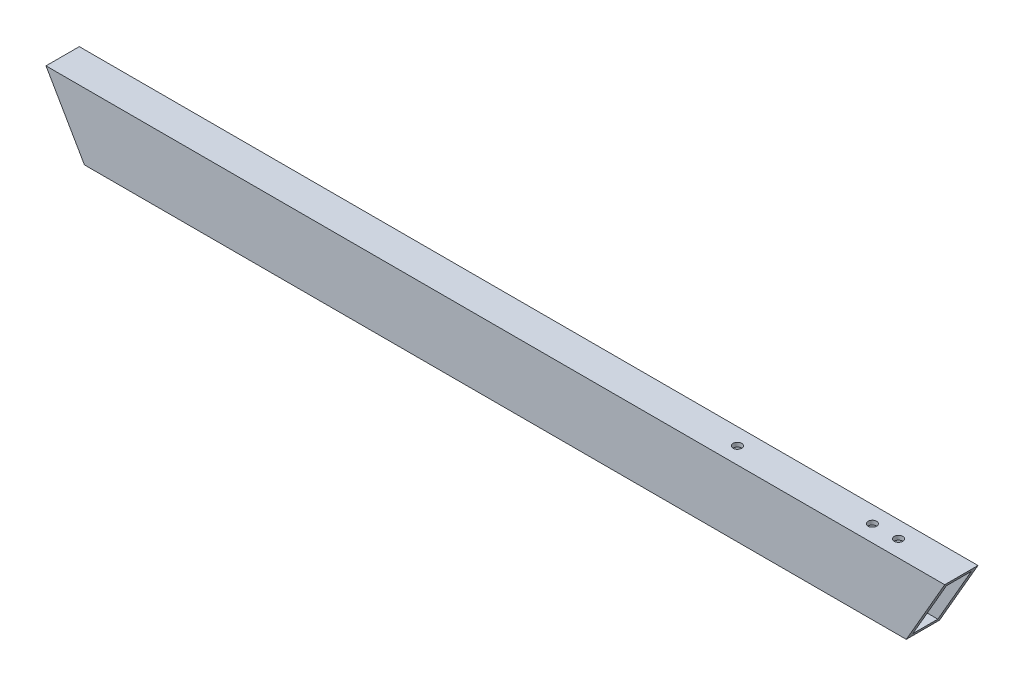
SolidWorks part; units mm, degrees
ref_plane "Front Plane" through (0, 0, 0) normal (0, 0, 1) x (1, 0, 0)
ref_plane "Top Plane" through (0, 0, 0) normal (0, 1, 0) x (1, 0, 0)
ref_plane "Right Plane" through (0, 0, 0) normal (1, 0, 0) x (0, 0, -1)
sketch "Sketch1" plane through (0, 0, 0) normal (1, 0, 0) x (0, 0, -1)
  line L1 (-9.525, -22.225) -> (9.525, -22.225)
  line L2 (-9.525, -22.225) -> (-9.525, 22.225)
  line L3 (-9.525, 22.225) -> (9.525, 22.225)
  line L4 (9.525, -22.225) -> (9.525, 22.225)
  line L5 (-9.525, -22.225) -> (9.525, 22.225) construction
  line L6 (-9.525, 22.225) -> (9.525, -22.225) construction
  line L7 (-12.7, -25.4) -> (12.7, -25.4)
  line L8 (-12.7, -25.4) -> (-12.7, 25.4)
  line L9 (-12.7, 25.4) -> (12.7, 25.4)
  line L10 (12.7, -25.4) -> (12.7, 25.4)
  line L11 (-12.7, -25.4) -> (12.7, 25.4) construction
  line L12 (-12.7, 25.4) -> (12.7, -25.4) construction
  point P0 (0, 0)
  point P6 (0, 0)
  dimension "D1" = 25.4
  dimension "D2" = 50.8
  dimension "D3" = 3.175
  dimension "D4" = 3.175
extrude "Boss-Extrude1" add sketch "Sketch1" along normal mid plane 685.8
sketch "Sketch2" plane through (0, 0, -12.7) normal (0, 0, -1) x (-1, 0, 0)
  line L0 (342.9, 25.4) -> (313.5706, -25.4)
  line L1 (-342.9, -25.4) -> (342.9, -25.4) construction
  line L3 (0, 13.97) -> (0, -13.97) construction
  line L4 (-342.9, 25.4) -> (-313.5706, -25.4)
  line M2 (342.9, -25.4) -> (342.9, 25.4)
  line M4 (-342.9, 25.4) -> (-342.9, -25.4)
  line M5 (-342.9, -25.4) -> (342.9, -25.4)
  dimension "D1" = 60
extrude "Cut-Extrude1" cut sketch "Sketch2" against normal through all and the other way through all contours L0 M2 M5 | L4 M4 M5 region at (-333.1235, -8.4667, -12.7) region at (333.1235, -8.4667, -12.7)
sketch "Sketch3" plane through (0, 0, -12.7) normal (0, 0, -1) x (-1, 0, 0)
  line L0 (-313.5706, -25.4) -> (313.5706, -25.4) construction
  circle A0 centre (-234.95, 0) radius 11.1125
  circle A1 centre (-190.5, 0) radius 11.1125
  dimension "D1" = 22.225
  dimension "D4" = 107.95
  dimension "D5" = 44.45
  dimension "D2" = 25.4
  dimension "D3" = 2
extrude "Cut-Extrude2" cut sketch "Sketch3" against normal up to next
hole_wizard "M6 Clearance Hole1" positions "Sketch5" profile "Sketch6" hole size "M6" standard "ANSI Metric" end condition up to next
sketch "Sketch5" plane through (0, 25.4, 0) normal (0, 1, 0) x (1, 0, 0)
  point P0 (294.9914, 0)
  point P3 (274.9914, 0)
  point P6 (171.9914, 0)
sketch "Sketch6" plane through (294.9914, 25.4, 0) normal (1, 0, 0) x (0, 0, 1)
  line L0 (0, 0) -> (0, 3.175)
  line L1 (0, 3.175) -> (3.3, 3.175)
  line L2 (3.3, 3.175) -> (3.3, 0)
  line L5 (3.3, 0) -> (0, 0)
  line L11 (0, -6.35) -> (0, 107.95) construction
  dimension "Thru Hole Dia." = 6.6
  dimension "Thru Hole Depth" = 3.175
